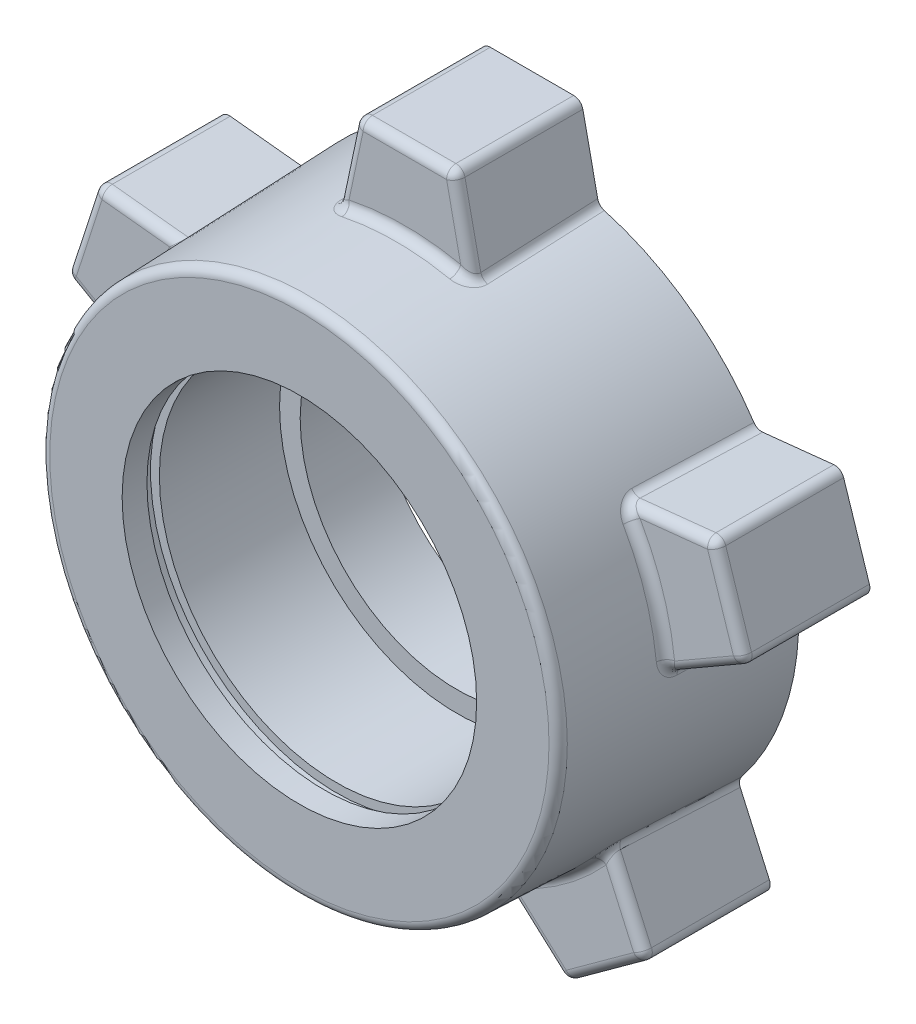
SolidWorks part; units mm, degrees
material "Gray Cast Iron"
ref_plane "Front Plane" through (0, 0, 0) normal (0, 0, 1) x (1, 0, 0)
ref_plane "Top Plane" through (0, 0, 0) normal (0, 1, 0) x (1, 0, 0)
ref_plane "Right Plane" through (0, 0, 0) normal (1, 0, 0) x (0, 0, -1)
sketch "Sketch1" plane through (0, 0, 0) normal (1, 0, 0) x (0, 0, -1)
  line L0 (76.7027, 0) -> (-80.5242, 0) construction
  line L1 (-75, 57.15) -> (-75, 83.3809)
  line L2 (-75, 83.3809) -> (0, 86)
  line L3 (0, 86) -> (0, 57.15)
  line L4 (0, 57.15) -> (-75, 57.15)
  dimension "D2" = 75
  dimension "D3" = 114.3
  dimension "D4" = 172
  dimension "D1" = 2
revolve "Revolve1" add sketch "Sketch1" angle 360 about L0
sketch "Sketch2" plane through (0, 0, 75) normal (0, 0, 1) x (1, 0, 0)
  line L0 (-24.8024, 68) -> (24.8024, 68)
  line L1 (-24.8024, 68) -> (-15.875, 110)
  line L2 (-15.875, 110) -> (15.875, 110)
  line L3 (15.875, 110) -> (24.8024, 68)
  line L4 (0, 192.306) -> (0, -135.1884) construction
  point P3 (0, 68)
  dimension "D1" = 110
  dimension "D2" = 12
  dimension "D3" = 31.75
  dimension "D4" = 42
extrude "Boss-Extrude1" add sketch "Sketch2" against normal through all from offset 34 offset against normal yes
pattern_circular "CirPattern1" count 5 over 360 about axis through (0, 0, -76.7027) along (0, 0, -1) of "Boss-Extrude1"
fillet "Fillet1" radius 3 33 edges at (-71.6125, -66.4384, 41) (-49.708, -68.4172, 41) (-41.0572, -88.6382, 41) (-51.8132, -98.323, 20.5) (-77.4995, -79.6608, 20.5) (-64.6564, -88.9919, 41) (41.0572, -88.6382, 41) (49.708, -68.4172, 41) (71.6125, -66.4384, 41) (77.4995, -79.6608, 20.5) (51.8132, -98.323, 20.5) (64.6564, -88.9919, 41) (99.7106, 49.0899, 20.5) (109.5219, 18.8938, 20.5) (104.6162, 33.9919, 41) (96.9873, 11.657, 41) (80.4292, 26.133, 41) (85.3161, 47.577, 41) (-15.875, 110, 20.5) (15.875, 110, 20.5) (0, 110, 41) (18.8843, 95.8426, 41) (0, 84.5682, 41) (-18.8843, 95.8426, 41) (-83.3809, 0, 75)
sketch "Sketch3" plane through (0, 0, 75) normal (0, 0, 1) x (1, 0, 0)
  circle A0 centre (0, 0) radius 60
  dimension "D1" = 120
extrude "Cut-Extrude1" cut sketch "Sketch3" against normal blind 4 from offset 8 offset against normal yes
sketch "Sketch4" plane through (0, 0, 0) normal (0, 0, -1) x (-1, 0, 0)
  circle A0 centre (0, 0) radius 50.5
  circle A1 centre (0, 0) radius 57.15
  circle A2 centre (0, 0) radius 57.15 construction
  dimension "D1" = 101
extrude "Boss-Extrude2" add sketch "Sketch4" against normal blind 24.25
fillet "Fillet2" radius 3 8 edges at (-104.6162, 33.9919, 41) (-85.3161, 47.577, 41) (-80.4292, 26.133, 41) (-96.9873, 11.657, 41) (-109.5219, 18.8938, 20.5) (-99.7106, 49.0899, 20.5)
equation "\"A\"= 75"
equation "\"B\"= 34"
equation "\"C\"= 172"
equation "\"D2@Sketch1\"=\"A\""
equation "\"D4@Sketch1\"=\"C\""
equation "\"D19@Boss-Extrude1\"=\"B\""
